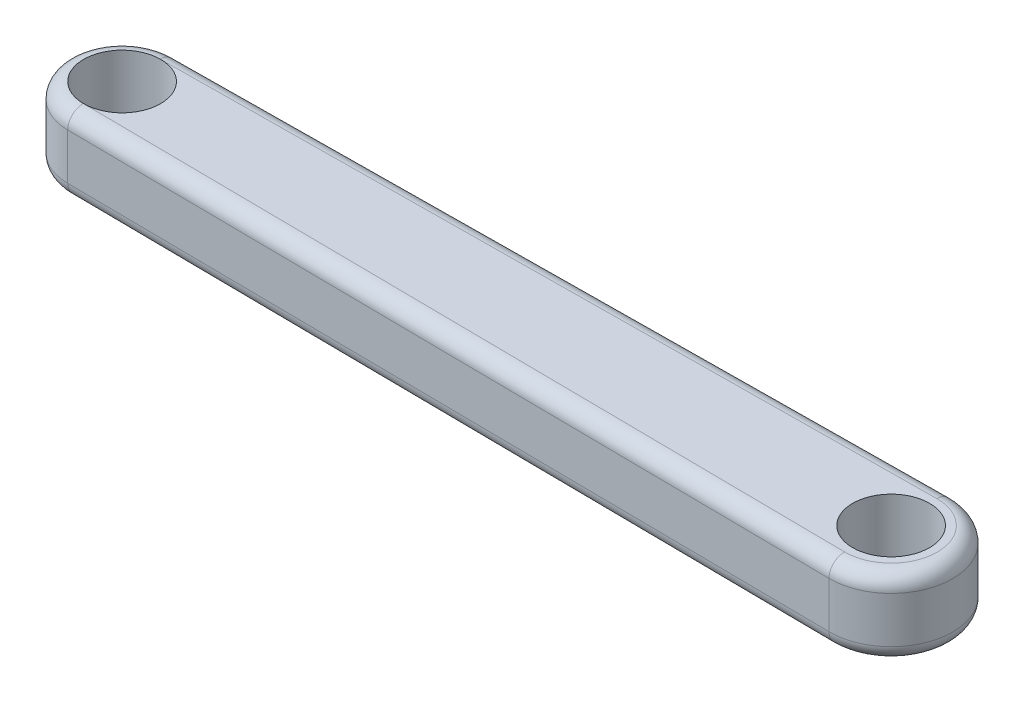
SolidWorks part; units mm, degrees
material "1060-H12"
ref_plane "Alzado" through (0, 0, 0) normal (0, 0, 1) x (1, 0, 0)
ref_plane "Planta" through (0, 0, 0) normal (0, 1, 0) x (1, 0, 0)
ref_plane "Vista lateral" through (0, 0, 0) normal (1, 0, 0) x (0, 0, -1)
sketch "Croquis1" plane through (0, 0, 0) normal (0, 1, 0) x (1, 0, 0)
  line L0 (-150.35, 34.9982) -> (349.6, 39.998)
  line L3 (0, 0) -> (0, 55) construction
  line L4 (-150, 0) -> (207.6415, 0) construction
  line L5 (-150.35, -34.9982) -> (349.6, -39.998)
  circle A2 centre (-150, 0) radius 25
  arc A4 (349.6, -39.998) -> (349.6, 39.998) centre (350, 0) ccw
  arc A5 (-150.35, 34.9982) -> (-150.35, -34.9982) centre (-150, 0) ccw
  circle A6 centre (350, 0) radius 25
  dimension "D3" = 50
  dimension "D4" = 80
  dimension "D1" = 70
  dimension "D2" = 50
  dimension "D5" = 500
  dimension "D6" = 150
extrude "Saliente-Extruir1" add sketch "Croquis1" along normal blind 50
fillet "Redondeo1" radius 10 8 edges at (390, 0, 0) (99.625, 0, 37.4981) (-185, 0, 0) (390, 50, 0) (99.625, 50, 37.4981) (-185, 50, 0) (99.625, 0, -37.4981) (99.625, 50, -37.4981)
